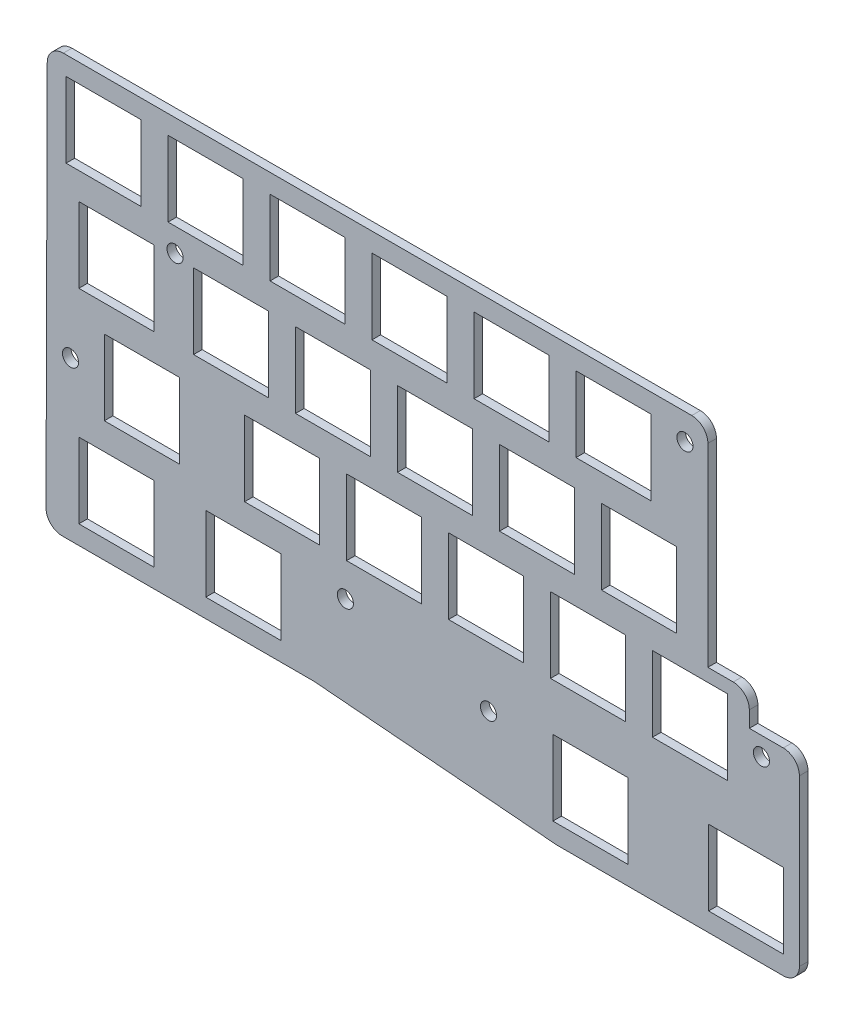
SolidWorks part; units mm, degrees
ref_plane "Front Plane" through (0, 0, 0) normal (0, 0, 1) x (1, 0, 0)
ref_plane "Top Plane" through (0, 0, 0) normal (0, 1, 0) x (1, 0, 0)
ref_plane "Right Plane" through (0, 0, 0) normal (1, 0, 0) x (0, 0, -1)
sketch "Sketch1" plane through (0, 0, 0) normal (0, 0, 1) x (1, 0, 0)
  line B0 (69.2565, 39.1549) -> (-80.7031, 39.0588)
  line B1 (9.8084, 35.5569) -> (-4.1916, 35.5569)
  line B2 (14.8084, 35.5569) -> (14.8084, 21.5569)
  line B3 (28.8084, 21.5569) -> (28.8084, 35.5569)
  line B4 (-28.1916, 35.5569) -> (-42.1916, 35.5569)
  circle B5 centre (35.1084, 34.2569) radius 1.5
  line B6 (28.8084, 35.5569) -> (14.8084, 35.5569)
  line B7 (-9.1916, 21.5569) -> (-9.1916, 35.5569)
  line B8 (-9.1916, 35.5569) -> (-23.1916, 35.5569)
  line B9 (-83.7012, 36.0684) -> (-83.9319, -35.9335)
  line B10 (-63.8166, 16.5569) -> (-77.8166, 16.5569)
  line B11 (-42.4416, 2.5569) -> (-42.4416, 16.5569)
  line B12 (-23.4416, 2.5569) -> (-23.4416, 16.5569)
  line B13 (-18.4416, 16.5569) -> (-18.4416, 2.5569)
  line B14 (-46.9416, -2.4431) -> (-46.9416, -16.4431)
  line B15 (-32.9416, -16.4431) -> (-32.9416, -2.4431)
  line B16 (5.0584, -2.4431) -> (-8.9416, -2.4431)
  line B17 (19.5584, 2.5569) -> (33.5584, 2.5569)
  line B18 (33.5584, 2.5569) -> (33.5584, 16.5569)
  line B19 (-77.8166, 16.5569) -> (-77.8166, 2.5569)
  line B20 (-8.9416, -2.4431) -> (-8.9416, -16.4431)
  line B21 (5.0584, -16.4431) -> (5.0584, -2.4431)
  line B22 (29.0584, -16.4431) -> (43.0584, -16.4431)
  line B23 (62.4422, -40.6918) -> (72.1045, -11.705)
  line B24 (10.5084, -25.2431) -> (10.5084, -39.2431)
  line B25 (-63.8166, -21.4431) -> (-77.8166, -21.4431)
  line B26 (-66.1916, 21.5569) -> (-66.1916, 35.5569)
  line B27 (-66.1916, 35.5569) -> (-80.1916, 35.5569)
  line B28 (-80.1916, 35.5569) -> (-80.1916, 21.5569)
  arc B29 (-80.7031, 39.0588) -> (-83.7012, 36.0684) centre (-80.7012, 36.0588) ccw
  arc B30 (-83.9319, -35.9335) -> (-80.932, -38.9431) centre (-80.932, -35.9431) ccw
  line B31 (-80.932, -38.9431) -> (-34.1624, -38.9431)
  arc B32 (-33.9113, -38.9537) -> (-34.1624, -38.9431) centre (-34.1624, -41.9431) ccw
  line B33 (-33.9113, -38.9537) -> (11.0831, -42.7326)
  arc B34 (11.0831, -42.7326) -> (11.3342, -42.7431) centre (11.3342, -39.7431) ccw
  line B35 (11.3342, -42.7431) -> (59.5961, -42.7431)
  arc B36 (59.5961, -42.7431) -> (62.4422, -40.6918) centre (59.5961, -39.7431) ccw
  arc B37 (72.1045, -11.705) -> (72.2584, -10.7563) centre (69.2584, -10.7563) ccw
  line B38 (72.2584, -10.7563) -> (72.2584, 36.1549)
  arc B39 (72.2584, 36.1549) -> (69.2565, 39.1549) centre (69.2584, 36.1549) ccw
  circle B40 centre (-28.1616, -22.7431) radius 1.5
  circle B41 centre (-1.4916, -27.4931) radius 1.5
  circle B42 centre (-79.3666, -9.4431) radius 1.5
  circle B43 centre (49.3584, -9.4431) radius 1.5
  circle B44 centre (-59.8916, 17.1569) radius 1.5
  line B45 (-80.1916, 21.5569) -> (-66.1916, 21.5569)
  line B46 (-61.1916, 21.5569) -> (-47.1916, 21.5569)
  line B47 (-47.1916, 21.5569) -> (-47.1916, 35.5569)
  line B48 (-47.1916, 35.5569) -> (-61.1916, 35.5569)
  line B49 (-61.1916, 35.5569) -> (-61.1916, 21.5569)
  line B50 (-42.1916, 21.5569) -> (-28.1916, 21.5569)
  line B51 (-28.1916, 21.5569) -> (-28.1916, 35.5569)
  line B52 (-42.1916, 35.5569) -> (-42.1916, 21.5569)
  line B53 (-23.1916, 21.5569) -> (-9.1916, 21.5569)
  line B54 (-23.1916, 35.5569) -> (-23.1916, 21.5569)
  line B55 (-4.1916, 21.5569) -> (9.8084, 21.5569)
  line B56 (9.8084, 21.5569) -> (9.8084, 35.5569)
  line B57 (-4.1916, 35.5569) -> (-4.1916, 21.5569)
  line B58 (14.8084, 21.5569) -> (28.8084, 21.5569)
  line B59 (-77.8166, 2.5569) -> (-63.8166, 2.5569)
  line B60 (-63.8166, 2.5569) -> (-63.8166, 16.5569)
  line B61 (-56.4416, 2.5569) -> (-42.4416, 2.5569)
  line B62 (-42.4416, 16.5569) -> (-56.4416, 16.5569)
  line B63 (-56.4416, 16.5569) -> (-56.4416, 2.5569)
  line B64 (-37.4416, 2.5569) -> (-23.4416, 2.5569)
  line B65 (-23.4416, 16.5569) -> (-37.4416, 16.5569)
  line B66 (-37.4416, 16.5569) -> (-37.4416, 2.5569)
  line B67 (-18.4416, 2.5569) -> (-4.4416, 2.5569)
  line B68 (-4.4416, 2.5569) -> (-4.4416, 16.5569)
  line B69 (-4.4416, 16.5569) -> (-18.4416, 16.5569)
  line B70 (0.5584, 2.5569) -> (14.5584, 2.5569)
  line B71 (14.5584, 2.5569) -> (14.5584, 16.5569)
  line B72 (14.5584, 16.5569) -> (0.5584, 16.5569)
  line B73 (0.5584, 16.5569) -> (0.5584, 2.5569)
  line B74 (33.5584, 16.5569) -> (19.5584, 16.5569)
  line B75 (19.5584, 16.5569) -> (19.5584, 2.5569)
  line B76 (-73.0666, -16.4431) -> (-59.0666, -16.4431)
  line B77 (-59.0666, -16.4431) -> (-59.0666, -2.4431)
  line B78 (-59.0666, -2.4431) -> (-73.0666, -2.4431)
  line B79 (-73.0666, -2.4431) -> (-73.0666, -16.4431)
  line B80 (-46.9416, -16.4431) -> (-32.9416, -16.4431)
  line B81 (-32.9416, -2.4431) -> (-46.9416, -2.4431)
  line B82 (-27.9416, -16.4431) -> (-13.9416, -16.4431)
  line B83 (-13.9416, -16.4431) -> (-13.9416, -2.4431)
  line B84 (-13.9416, -2.4431) -> (-27.9416, -2.4431)
  line B85 (-27.9416, -2.4431) -> (-27.9416, -16.4431)
  line B86 (-8.9416, -16.4431) -> (5.0584, -16.4431)
  line B87 (10.0584, -16.4431) -> (24.0584, -16.4431)
  line B88 (24.0584, -16.4431) -> (24.0584, -2.4431)
  line B89 (24.0584, -2.4431) -> (10.0584, -2.4431)
  line B90 (10.0584, -2.4431) -> (10.0584, -16.4431)
  line B91 (43.0584, -16.4431) -> (43.0584, -2.4431)
  line B92 (43.0584, -2.4431) -> (29.0584, -2.4431)
  line B93 (29.0584, -2.4431) -> (29.0584, -16.4431)
  line B94 (-77.8166, -35.4431) -> (-63.8166, -35.4431)
  line B95 (-63.8166, -35.4431) -> (-63.8166, -21.4431)
  line B96 (-77.8166, -21.4431) -> (-77.8166, -35.4431)
  line B97 (-54.1616, -35.4431) -> (-40.1616, -35.4431)
  line B98 (-40.1616, -35.4431) -> (-40.1616, -21.4431)
  line B99 (-40.1616, -21.4431) -> (-54.1616, -21.4431)
  line B100 (-54.1616, -21.4431) -> (-54.1616, -35.4431)
  line B101 (10.5084, -39.2431) -> (24.5084, -39.2431)
  line B102 (24.5084, -39.2431) -> (24.5084, -25.2431)
  line B103 (24.5084, -25.2431) -> (10.5084, -25.2431)
  line B104 (39.5084, -39.2431) -> (53.5084, -39.2431)
  line B105 (53.5084, -39.2431) -> (53.5084, -25.2431)
  line B106 (53.5084, -25.2431) -> (39.5084, -25.2431)
  line B107 (39.5084, -25.2431) -> (39.5084, -39.2431)
sketch_block_instance "switch_plate (1)-1"
sketch_block "switch_plate (1)"
extrude "Boss-Extrude1" add sketch "Sketch1" along normal blind 1.6
sketch "Sketch2" plane through (0, 0, 1.6) normal (0, 0, 1) x (1, 0, 0)
  line L0 (39.3773, 41.9719) -> (39.3773, 0)
  line L1 (39.3773, 0) -> (47.1007, 0)
  line L2 (47.1007, 0) -> (47.1007, -5.9776)
  line L3 (47.1007, -5.9776) -> (56.4332, -5.9776)
  line L4 (56.4332, -5.9776) -> (56.4332, -45.2383)
  line L5 (56.4332, -45.2383) -> (88.4532, -41.8593)
  line L6 (88.4532, -41.8593) -> (93.4412, 41.9719)
  line L7 (93.4412, 41.9719) -> (39.3773, 41.9719)
extrude "Cut-Extrude1" cut sketch "Sketch2" against normal blind 1.6
fillet "Fillet1" radius 3 4 edges at (56.4332, -42.7431, 0.8) (56.4332, -5.9776, 0.8) (47.1007, 0, 0.8) (39.3773, 39.1358, 0.8)
